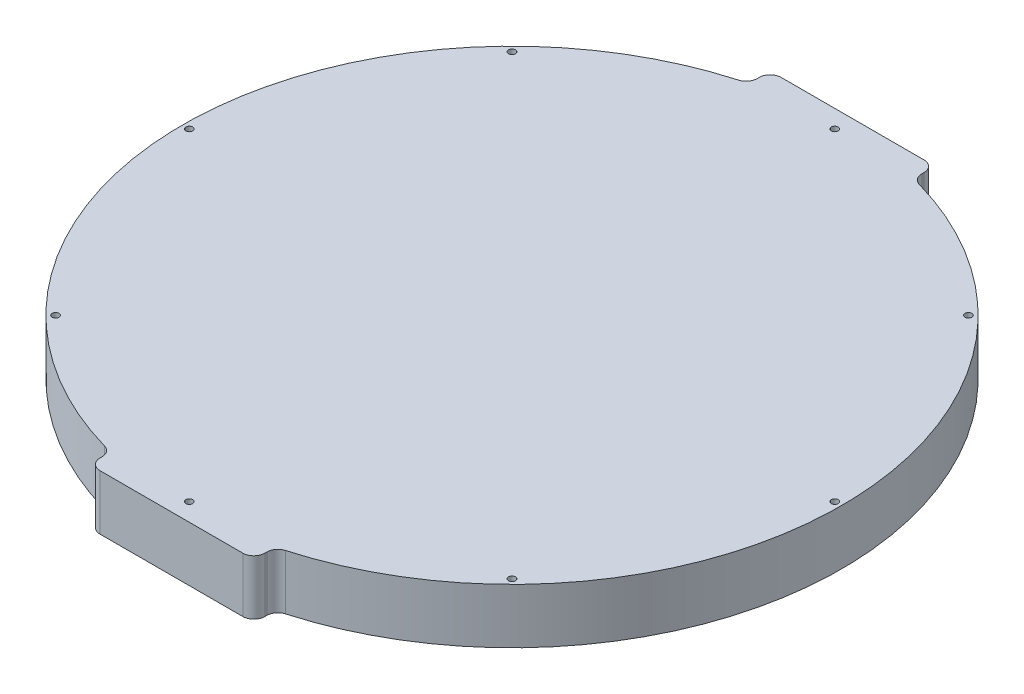
SolidWorks part; units mm, degrees
material "6061 Alloy"
ref_plane "Front Plane" through (0, 0, 0) normal (0, 0, 1) x (1, 0, 0)
ref_plane "Top Plane" through (0, 0, 0) normal (0, 1, 0) x (1, 0, 0)
ref_plane "Right Plane" through (0, 0, 0) normal (1, 0, 0) x (0, 0, -1)
sketch "Sketch2" plane through (0, 0, 0) normal (0, 1, 0) x (1, 0, 0)
  circle A0 centre (0, 0) radius 76.2
extrude "Boss-Extrude1" add sketch "Sketch2" along normal blind 12.7
sketch "Sketch3" plane through (0, 0, 0) normal (0, 0, 1) x (1, 0, 0)
  line L0 (0, 0) -> (-19.05, 0)
  line L1 (-19.05, 0) -> (-19.05, 12.7)
  line L2 (-19.05, 12.7) -> (19.05, 12.7)
  line L3 (19.05, 12.7) -> (19.05, 0)
  line L4 (0, 0) -> (19.05, 0)
extrude "Boss-Extrude2" add sketch "Sketch3" along normal blind 78.74 and the other way blind 78.74
fillet "Fillet1" radius 2.54 8 edges at (19.05, 6.35, 73.7803) (19.05, 6.35, 78.74) (-19.05, 6.35, 73.7803) (-19.05, 6.35, 78.74) (-19.05, 6.35, -73.7803) (-19.05, 6.35, -78.74) (19.05, 6.35, -73.7803) (19.05, 6.35, -78.74)
sketch "Sketch4" plane through (0, 12.7, 0) normal (0, 1, 0) x (1, 0, 0)
  circle A0 centre (74.6125, 0) radius 0.7937
  circle A1 centre (52.759, -52.759) radius 0.7937
  circle A2 centre (0, -74.6125) radius 0.7937
  circle A3 centre (-52.759, -52.759) radius 0.7937
  circle A4 centre (-74.6125, 0) radius 0.7937
  circle A5 centre (-52.759, 52.759) radius 0.7937
  circle A6 centre (0, 74.6125) radius 0.7937
  circle A7 centre (52.759, 52.759) radius 0.7937
  point P18 (0, 0)
  dimension "D1" = 8
extrude "Cut-Extrude1" cut sketch "Sketch4" against normal through all
